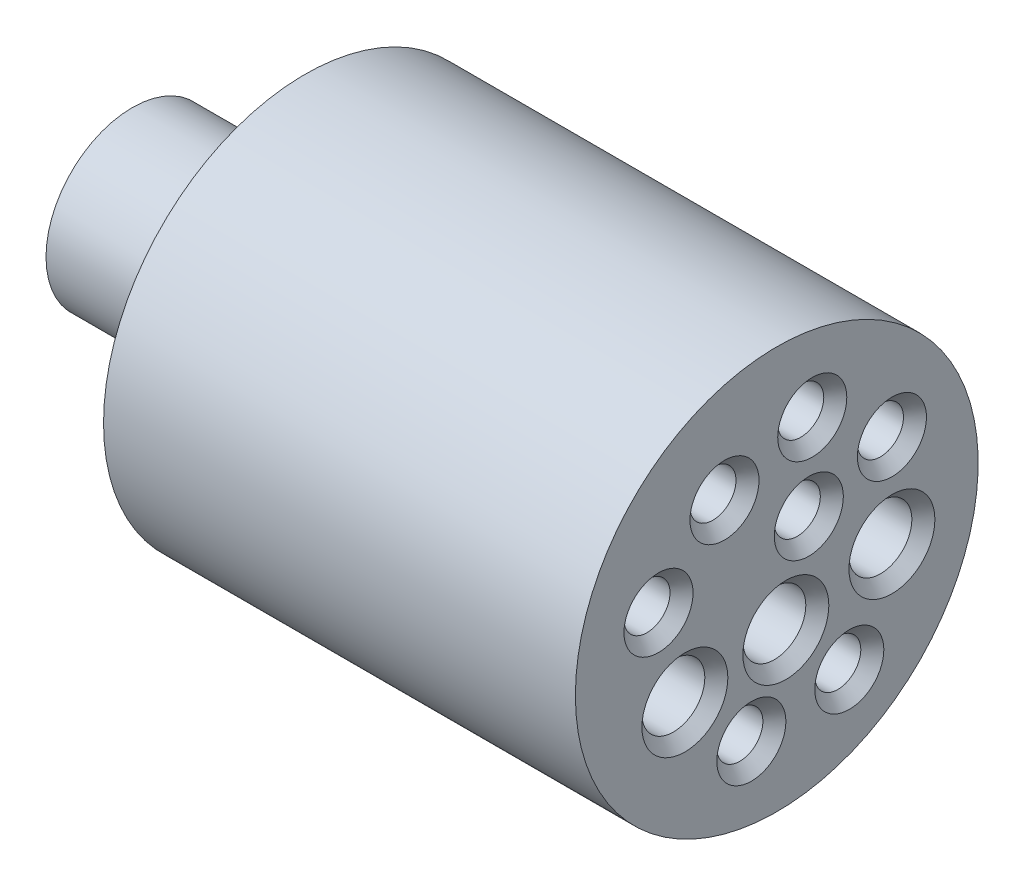
SolidWorks part; units mm, degrees
ref_plane "Front Plane" through (0, 0, 0) normal (0, 0, 1) x (1, 0, 0)
ref_plane "Top Plane" through (0, 0, 0) normal (0, 1, 0) x (1, 0, 0)
ref_plane "Right Plane" through (0, 0, 0) normal (1, 0, 0) x (0, 0, -1)
sketch "Sketch3" plane through (0, 0, 0) normal (0, 0, 1) x (1, 0, 0)
  line L0 (0, 0) -> (0, -50000) construction
  line L1 (0, 0) -> (50000, 0) construction
  line L2 (45.5, 0) -> (45.5, 17.5)
  line L3 (45.5, 17.5) -> (0, 17.5)
  line L4 (0, 17.5) -> (-9.5, 15.75)
  line L5 (-9.5, 15.75) -> (-25.5, 15.75)
  line L6 (-25.5, 15.75) -> (-25.5, 20.5)
  line L7 (-45.5, 0) -> (-45.5, 53.8042) construction
  line L8 (-25.5, 20.5) -> (-31.1909, 20.5)
  line L9 (-45.5, 10) -> (-36.3733, 10) construction
  line L10 (-45.5, 10) -> (-45.5, 0)
  line L11 (-45.5, 0) -> (45.5, 0)
  arc A0 (-45.5, 10) -> (-38.8224, 14.9) centre (-45.5, 17) ccw
  arc A1 (-38.8224, 14.9) -> (-31.1909, 20.5) centre (-31.1909, 12.5) cw
  dimension "D8" = 20
  dimension "D9" = 7
  dimension "D10" = 8
  dimension "D1" = 17.5
  dimension "D2" = 45.5
  dimension "D3" = 9.5
  dimension "D4" = 31.5
  dimension "D5" = 41
  dimension "D6" = 71
  dimension "D7" = 20
revolve "Revolve1" add sketch "Sketch3" angle 360 about L1
fillet "Fillet1" radius 5 1 edges at (-25.5, 0, 15.75)
fillet "Fillet2" radius 0.3 1 edges at (-25.5, 0, 20.5)
fillet "Fillet3" radius 5 2 edges at (0, 0, 17.5) (-9.5, 0, 15.75)
sketch "Sketch6" plane through (45.5, 0, 0) normal (1, 0, 0) x (0, 0, -1)
  line L0 (-16.3442, -6.4134) -> (3.8869, -6.4134) construction
  circle A0 centre (2.7838, 3.3454) radius 2.0006
  circle A1 centre (3.0831, 10.6474) radius 2.0006
  circle A2 centre (-4.5453, 8.2222) radius 2.0006
  circle A3 centre (-10.2777, 2.6222) radius 2.0006
  circle A4 centre (10.006, 5.7088) radius 2.0006
  circle A5 centre (-2.2083, -11.0914) radius 2.0006
  circle A6 centre (6.302, -9.9449) radius 2.0006
  circle A7 centre (10.006, -2.3606) radius 2.7332
  circle A8 centre (0.7901, -4.2126) radius 2.7332
  circle A9 centre (-7.9847, -5.2708) radius 2.7332
extrude "Cut-Extrude1" cut sketch "Sketch6" against normal blind 21
chamfer "Chamfer1" distance 1 angle 45 10 edges at (45.5, -5.2708, 5.2516) (45.5, -11.0914, 0.2077) (45.5, -9.9449, -8.3026) (45.5, -4.2126, -3.5233) (45.5, 3.3454, -4.7844) (45.5, -2.3606, -12.7391) (45.5, 5.7088, -12.0066) (45.5, 10.6474, -5.0837) (45.5, 8.2222, 2.5447) (45.5, 2.6222, 8.2771)
sketch "Sketch7" plane through (-45.5, 0, 0) normal (-1, 0, 0) x (0, 0, 1)
  circle A0 centre (0, 0) radius 7.5
  dimension "D1" = 15
extrude "Extrude-Thin1" add sketch "Sketch7" along normal blind 15 thin thin type one direction reverse wall 0.5
sketch "Sketch8" plane through (0, 0, 0) normal (0, 0, 1) x (1, 0, 0)
  line L0 (-45.5, 10) -> (-45.5, -49990) construction
  line L3 (-45.5, 24.8575) -> (4.5, 24.8575)
  line L4 (-45.5, 24.8575) -> (-45.5, -25.1425)
  line L5 (-45.5, -25.1425) -> (4.5, -25.1425)
  line L6 (4.5, 24.8575) -> (4.5, -25.1425)
  dimension "D1" = 50
extrude "Cut-Extrude2" cut sketch "Sketch8" along normal through all both and the other way through all
move or copy body "Body-Move/Copy1" bodies to move or copy 107 copy no translate (-50, 0, 0)
